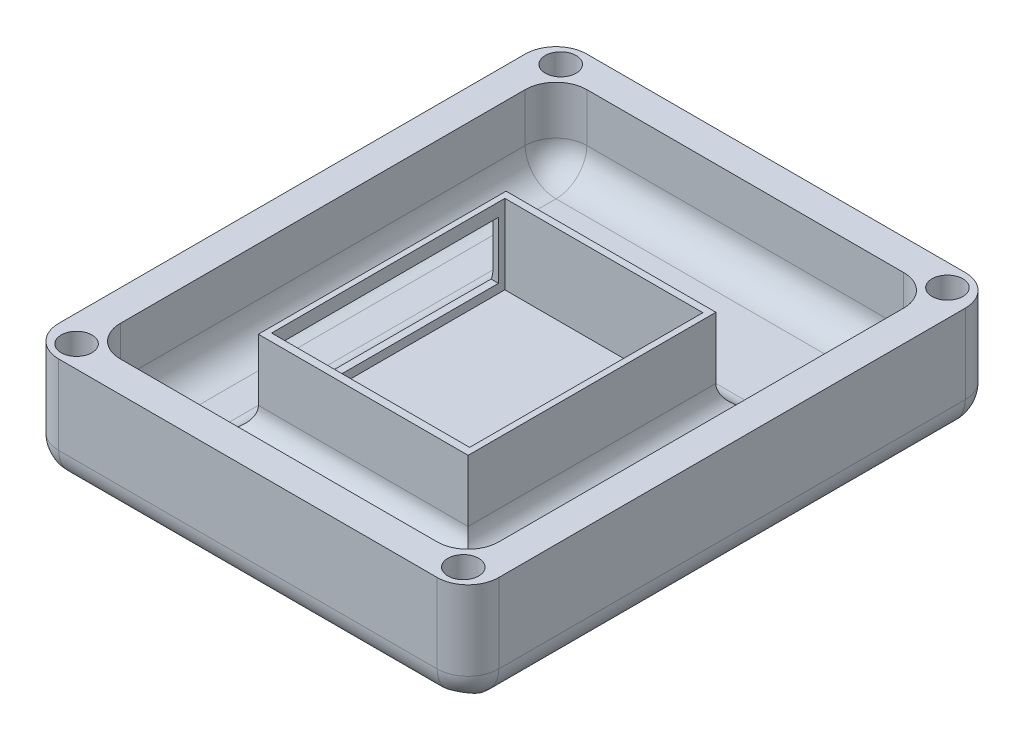
SolidWorks part; units mm, degrees
ref_plane "Front Plane" through (0, 0, 0) normal (0, 0, 1) x (1, 0, 0)
ref_plane "Top Plane" through (0, 0, 0) normal (0, 1, 0) x (1, 0, 0)
ref_plane "Right Plane" through (0, 0, 0) normal (1, 0, 0) x (0, 0, -1)
sketch "Sketch1" plane through (0, 0, 0) normal (0, 1, 0) x (1, 0, 0)
  line L1 (-50, 60) -> (50, 60)
  line L2 (-50, 60) -> (-50, -60)
  line L3 (-50, -60) -> (50, -60)
  line L4 (50, 60) -> (50, -60)
  line L5 (0, -60) -> (0, 60) construction
  line L6 (-50, 0) -> (50, 0) construction
  point P0 (0, 0)
  dimension "D1" = 120
  dimension "D2" = 100
extrude "Boss-Extrude1" add sketch "Sketch1" along normal blind 25
fillet "Fillet1" radius 7 8 edges at (0, 0, -60) (-50, 0, 0) (0, 0, 60) (50, 0, 0) (-50, 12.5, 60) (-50, 12.5, -60) (50, 12.5, -60) (50, 12.5, 60)
shell "Shell2" thickness 7 removed face at (0, 25, 0)
other "Groove1" [suppressed] parameters "GrooveHeight"=2, "GrooveWidth"=1, "GrooveDraftAngle"=3, "D4"=0, "D5"=0, "D6"=2, "D7"=1, "D8"=3, "D9"=0
fillet "Fillet2" radius 7 1 edges at (0, 7, 53)
fillet "Fillet3" radius 7 3 edges at (43, 19.5, 53) (43, 9.0503, 50.9497) (43, 7, -3.5)
fillet "Fillet4" radius 7 3 edges at (43, 19.5, -53) (40.9497, 9.0503, -53) (-3.5, 7, -53)
fillet "Fillet5" radius 7 5 edges at (-43, 19.5, -53) (-43, 9.0503, -50.9497) (-43, 19.5, 53) (-43, 9.0503, 50.9497) (-43, 7, 0)
sketch "Sketch2" plane through (0, 25, 0) normal (0, 1, 0) x (1, 0, 0)
  line L0 (-43, 46) -> (-36, 46) construction
  line L1 (-43, -46) -> (-36, -46) construction
  line L2 (43, 46) -> (36, 46) construction
  line L3 (43, -46) -> (36, -46) construction
  circle A0 centre (-43.9373, 55) radius 3.5
  circle A1 centre (-43.9373, -55) radius 3.5
  circle A2 centre (43.9373, 55) radius 3.5
  circle A3 centre (43.9373, -55) radius 3.5
  dimension "D1" = 7
  dimension "D4" = 7
  dimension "D7" = 7
  dimension "D10" = 7
  dimension "D2" = 12
  dimension "D3" = 9
  dimension "D5" = 12
  dimension "D6" = 9
  dimension "D8" = 12
  dimension "D9" = 9
  dimension "D11" = 12
  dimension "D12" = 9
extrude "Cut-Extrude1" cut sketch "Sketch2" against normal through all
sketch "Sketch3" plane through (0, 7, 0) normal (0, 1, 0) x (1, 0, 0)
  line L1 (-22.9129, 21.2864) -> (22.0871, 21.2864)
  line L2 (-22.9129, 21.2864) -> (-22.9129, -31.7136)
  line L3 (-22.9129, -31.7136) -> (22.0871, -31.7136)
  line L4 (22.0871, 21.2864) -> (22.0871, -31.7136)
  dimension "D1" = 45
  dimension "D2" = 53
sketch "Sketch5" plane through (0, 7, 0) normal (0, 1, 0) x (1, 0, 0)
  line L1 (-24.1858, 22.8422) -> (23.4787, 22.8422)
  line L2 (-24.1858, 22.8422) -> (-24.1858, -33.45)
  line L3 (-24.1858, -33.45) -> (23.4787, -33.45)
  line L4 (23.4787, 22.8422) -> (23.4787, -33.45)
extrude "Boss-Extrude3" add sketch "Sketch5" along normal blind 19 contours L1 L4 L3 L2
sketch "Sketch7" plane through (0, 26, 0) normal (0, 1, 0) x (1, 0, 0)
  line L1 (-22.9129, 21.2864) -> (22.0871, 21.2864)
  line L2 (-22.9129, 21.2864) -> (-22.9129, -31.7136)
  line L3 (-22.9129, -31.7136) -> (22.0871, -31.7136)
  line L4 (22.0871, 21.2864) -> (22.0871, -31.7136)
extrude "Cut-Extrude3" cut sketch "Sketch7" against normal blind 18
ref_plane "Plane1" through (43, 7, 60) normal (0, 1, 0) x (1, 0, 0)
sketch "Sketch9" plane through (-24.1858, 0, 0) normal (-1, 0, 0) x (0, 0, 1)
  line L0 (-22.8422, 26) -> (-22.8422, 7) construction
  line L1 (-19.8422, 23) -> (30.45, 23)
  line L2 (-19.8422, 23) -> (-19.8422, 10)
  line L3 (-19.8422, 10) -> (30.45, 10)
  line L4 (30.45, 23) -> (30.45, 10)
  line L5 (33.45, 26) -> (33.45, 7) construction
  line L6 (-22.8422, 26) -> (33.45, 26) construction
  line L7 (-21.2864, 7) -> (31.7136, 7) construction
  dimension "D1" = 3
  dimension "D2" = 3
  dimension "D3" = 3
  dimension "D4" = 3
extrude "Cut-Extrude4" cut sketch "Sketch9" against normal up to next
fillet "Fillet6" radius 5 1 edges at (23.4787, 7, 5.3039)
fillet "Fillet7" radius 5 1 edges at (2.1464, 7, -22.8422)
fillet "Fillet8" radius 5 1 edges at (-24.1858, 7, 2.8039)
fillet "Fillet9" radius 5 1 edges at (-0.3536, 7, 33.45)
sketch "Sketch11" plane through (0, 0, 0) normal (0, -1, 0) x (-1, 0, 0)
  text T0 "Wavelength" font "Century Schoolbook" height 3.5
extrude "Cut-Extrude5" cut sketch "Sketch11" against normal blind 1
